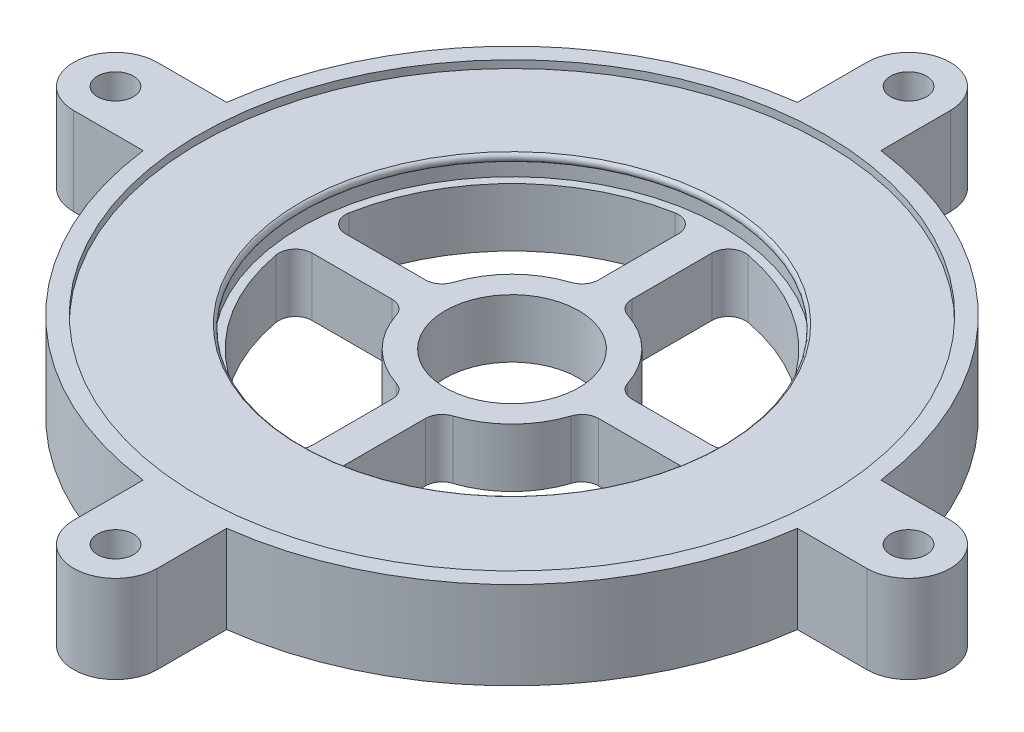
SolidWorks part; units mm, degrees
ref_plane "Front Plane" through (0, 0, 0) normal (0, 0, 1) x (1, 0, 0)
ref_plane "Top Plane" through (0, 0, 0) normal (0, 1, 0) x (1, 0, 0)
ref_plane "Right Plane" through (0, 0, 0) normal (1, 0, 0) x (0, 0, -1)
sketch "Sketch1" plane through (0, 0, 0) normal (1, 0, 0) x (0, 0, -1)
  line L0 (-37.5, -1.0482) -> (-37.5, -1.9554)
  line L1 (-37.5, -1.9554) -> (-25.3, -1.9554)
  line L2 (-25.3, -2.9554) -> (-25.3, -4.5554)
  line L3 (-25.3, -4.5554) -> (-8, -4.5554)
  line L4 (-8, -4.5554) -> (-8, -11.5554)
  line L5 (-8, -11.5554) -> (-39.5, -11.5554)
  line L6 (-39.5, -11.5554) -> (-39.5, -1.0482)
  line L9 (-39.5, -1.0482) -> (-37.5, -1.0482)
  line L10 (0, -1000) -> (0, 49000) construction
  arc A0 (-25.3, -1.9554) -> (-25.3, -2.9554) centre (-25.5667, -2.4554) cw
  point P13 (-25, -2.4554)
  point P17 (-37.5, -1.5018)
  dimension "D2" = 1.6
  dimension "D4" = 1
  dimension "D1" = 25.3
  dimension "D3" = 0.3
  dimension "D5" = 37.5
  dimension "D6" = 7
  dimension "D7" = 2
  dimension "D8" = 8
revolve "Revolve1" add sketch "Sketch1" angle 360 about L10 region at (0, -7.3219, 25.0852)
sketch "Sketch2" plane through (0, -11.5554, 0) normal (0, -1, 0) x (1, 0, 0)
  line L0 (0, 0) -> (0, 47.5) construction
  line L1 (-5, 47.5) -> (-5, 39.1823)
  line L2 (5, 47.5) -> (5, 39.1823)
  line L3 (5, 39.1823) -> (-5, 39.1823)
  line L4 (47.5, -5) -> (39.1823, -5)
  line L5 (47.5, 5) -> (39.1823, 5)
  line L6 (39.1823, -5) -> (39.1823, 5)
  line L7 (-5, -47.5) -> (-5, -39.1823)
  line L8 (5, -47.5) -> (5, -39.1823)
  line L9 (-5, -39.1823) -> (5, -39.1823)
  line L10 (-47.5, 5) -> (-39.1823, 5)
  line L11 (-47.5, -5) -> (-39.1823, -5)
  line L12 (-39.1823, 5) -> (-39.1823, -5)
  circle A0 centre (0, 47.5) radius 2.15
  arc A1 (5, 47.5) -> (-5, 47.5) centre (0, 47.5) ccw
  circle A2 centre (0, 0) radius 39.5 construction
  arc A3 (47.5, -5) -> (47.5, 5) centre (47.5, 0) ccw
  arc A4 (-5, -47.5) -> (5, -47.5) centre (0, -47.5) ccw
  arc A5 (-47.5, 5) -> (-47.5, -5) centre (-47.5, 0) ccw
  circle A6 centre (47.5, 0) radius 2.15
  circle A7 centre (0, -47.5) radius 2.15
  circle A8 centre (-47.5, 0) radius 2.15
  point P28 (0, 0)
  dimension "D2" = 4.3
  dimension "D3" = 10
  dimension "D1" = 47.5
  dimension "D4" = 4
extrude "Boss-Extrude1" add sketch "Sketch2" against normal up to surface (10.5072 mm away) up to face at (0, -1.0482, -37.5)
sketch "Sketch3" plane through (0, -4.5554, 0) normal (0, 1, 0) x (1, 0, 0)
  line L0 (0, 0) -> (50000, 0) construction
  line L1 (21.9383, -2) -> (12.3693, -2)
  line L2 (2, -12.3693) -> (2, -21.9383)
  line L3 (0, -0.3712) -> (0, -50000.3712) construction
  line L4 (-2, -21.9383) -> (-2, -12.3693)
  line L5 (-12.3693, -2) -> (-21.9383, -2)
  line L6 (-21.9383, 2) -> (-12.3693, 2)
  line L7 (-2, 12.3693) -> (-2, 21.9383)
  line L8 (2, 21.9383) -> (2, 12.3693)
  line L9 (12.3693, 2) -> (21.9383, 2)
  arc A1 (3.3846, -10.4663) -> (10.4663, -3.3846) centre (0, 0) ccw
  circle A2 centre (0, 0) radius 8 construction
  arc A4 (4.3587, -23.9059) -> (23.9059, -4.3587) centre (0, 0) ccw
  arc A5 (2, -12.3693) -> (3.3846, -10.4663) centre (4, -12.3693) cw
  arc A6 (2, -21.9383) -> (4.3587, -23.9059) centre (4, -21.9383) ccw
  arc A7 (21.9383, -2) -> (23.9059, -4.3587) centre (21.9383, -4) cw
  arc A8 (12.3693, -2) -> (10.4663, -3.3846) centre (12.3693, -4) ccw
  arc A9 (-23.9059, -4.3587) -> (-4.3587, -23.9059) centre (0, 0) ccw
  arc A10 (-2, -21.9383) -> (-4.3587, -23.9059) centre (-4, -21.9383) cw
  arc A11 (-2, -12.3693) -> (-3.3846, -10.4663) centre (-4, -12.3693) ccw
  arc A12 (-10.4663, -3.3846) -> (-3.3846, -10.4663) centre (0, 0) ccw
  arc A13 (-12.3693, -2) -> (-10.4663, -3.3846) centre (-12.3693, -4) cw
  arc A14 (-21.9383, -2) -> (-23.9059, -4.3587) centre (-21.9383, -4) ccw
  arc A15 (-4.3587, 23.9059) -> (-23.9059, 4.3587) centre (0, 0) ccw
  arc A16 (-21.9383, 2) -> (-23.9059, 4.3587) centre (-21.9383, 4) cw
  arc A17 (-12.3693, 2) -> (-10.4663, 3.3846) centre (-12.3693, 4) ccw
  arc A18 (-3.3846, 10.4663) -> (-10.4663, 3.3846) centre (0, 0) ccw
  arc A19 (-2, 12.3693) -> (-3.3846, 10.4663) centre (-4, 12.3693) cw
  arc A20 (-2, 21.9383) -> (-4.3587, 23.9059) centre (-4, 21.9383) ccw
  arc A21 (23.9059, 4.3587) -> (4.3587, 23.9059) centre (0, 0) ccw
  arc A22 (2, 21.9383) -> (4.3587, 23.9059) centre (4, 21.9383) cw
  arc A23 (2, 12.3693) -> (3.3846, 10.4663) centre (4, 12.3693) ccw
  arc A24 (10.4663, 3.3846) -> (3.3846, 10.4663) centre (0, 0) ccw
  arc A25 (12.3693, 2) -> (10.4663, 3.3846) centre (12.3693, 4) cw
  arc A26 (21.9383, 2) -> (23.9059, 4.3587) centre (21.9383, 4) ccw
  point P59 (0, 0)
  dimension "D2" = 2
  dimension "D1" = 3
  dimension "D3" = 2
  dimension "D4" = 2
  dimension "D5" = 4
extrude "Cut-Extrude2" cut sketch "Sketch3" against normal up to surface (7 mm away) up to face at (0, -11.5554, 0)
sketch "Sketch4" plane through (0, -11.5554, 0) normal (0, -1, 0) x (-1, 0, 0)
  line L0 (0, 0) -> (21.2132, -21.2132) construction
  line L1 (0, 0) -> (50000, 0) construction
  circle A0 centre (21.2132, -21.2132) radius 2.15
  circle A1 centre (-21.2132, -21.2132) radius 2.15
  circle A2 centre (-21.2132, 21.2132) radius 2.15
  circle A3 centre (21.2132, 21.2132) radius 2.15
  point P15 (0, 0)
  dimension "D3" = 4.3
  dimension "D1" = 45
  dimension "D2" = 30
  dimension "D4" = 4
extrude "Cut-Extrude3" cut sketch "Sketch4" against normal blind 7
equation "\"D4@Sketch3\"=\"D3@Sketch3\""
